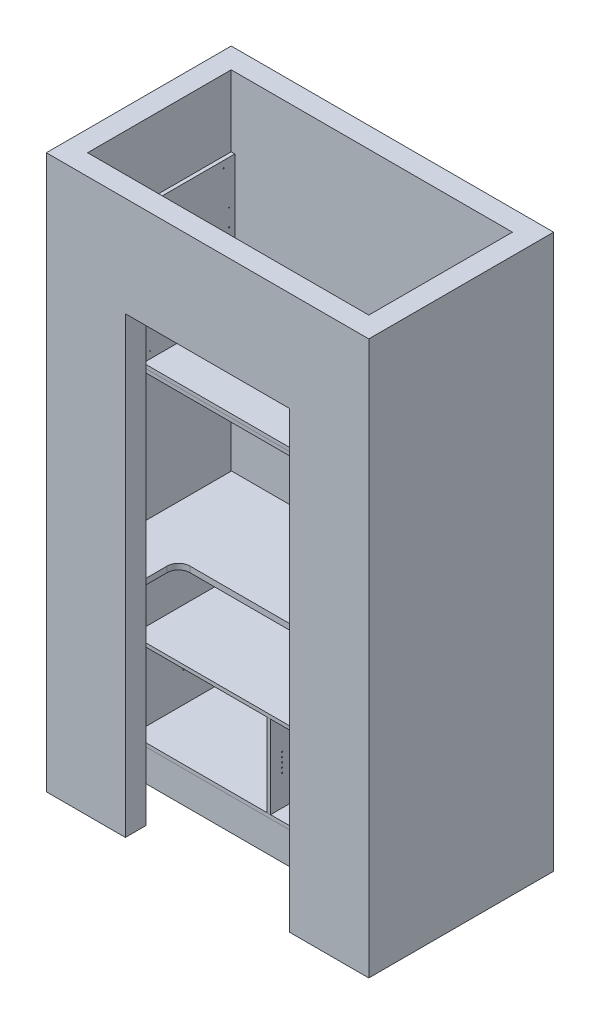
SolidWorks part; units mm, degrees
ref_plane "Front" through (0, 0, 0) normal (0, 0, 1) x (1, 0, 0)
ref_plane "Top" through (0, 0, 0) normal (0, 1, 0) x (1, 0, 0)
ref_plane "Right" through (0, 0, 0) normal (1, 0, 0) x (0, 0, -1)
sketch "Sketch1" plane through (0, 0, 0) normal (0, 1, 0) x (1, 0, 0)
  line L0 (-90, 90) -> (1317.5, 90)
  line L1 (0, 0) -> (1227.5, 0)
  line L2 (0, 0) -> (0, -627)
  line L3 (0, -627) -> (255, -627)
  line L4 (1227.5, 0) -> (1227.5, -627)
  line L5 (1317.5, 90) -> (1317.5, -717)
  line L6 (-90, -717) -> (255, -717)
  line L7 (-90, 90) -> (-90, -717)
  line L8 (255, -627) -> (255, -717)
  line L9 (972.5, -627) -> (972.5, -717)
  line L10 (972.5, -717) -> (1317.5, -717)
  line L11 (972.5, -627) -> (1227.5, -627)
  line L12 (-90, -717) -> (1317.5, -717) construction
  line L13 (255, -627) -> (972.5, -627)
  line L14 (0, -627) -> (1227.5, -627) construction
  line L15 (255, -717) -> (972.5, -717)
  dimension "D1" = 1227.5
  dimension "D2" = 627
  dimension "D4" = 255
  dimension "D5" = 255
  dimension "D3" = 90
extrude "Boss-Extrude1" add sketch "Sketch1" along normal blind 2416 contours L11 L9 L10 L5 L0 L7 L6 L8 L3 L2 L1 L4 | L8 L15 L9 L13 region at (613.75, 0, -73.7756) region at (613.75, 0, 672)
sketch "Sketch2" plane through (0, 0, 717) normal (0, 0, 1) x (1, 0, 0)
  line L0 (-90, 0) -> (1317.5, 0) construction
  line L1 (255, 0) -> (972.5, 0)
  line L2 (255, 0) -> (255, 1980)
  line L3 (255, 1980) -> (972.5, 1980)
  line L4 (972.5, 0) -> (972.5, 1980)
  line L5 (0, 2416) -> (0, 0) construction
  line L6 (1227.5, 2416) -> (1227.5, 0) construction
  dimension "D1" = 255
  dimension "D2" = 255
  dimension "D3" = 1980
  dimension "D4" = 717.5
extrude "Cut-Extrude1" cut sketch "Sketch2" against normal blind 100
sketch "Sketch4" plane through (0, 0, 0) normal (0, 0, 1) x (1, 0, 0)
  line L0 (1227.5, 2416) -> (1227.5, 0) construction
  line L5 (0, 120) -> (1227.5, 120)
  line L7 (16, 136) -> (1211.5, 136)
  line L9 (16, 513.5) -> (605.75, 513.5)
  line L11 (16, 497.5) -> (605.75, 497.5)
  line L13 (16, 875) -> (1211.5, 875)
  line L15 (16, 900) -> (1211.5, 900)
  line L21 (16, 1500) -> (1211.5, 1500)
  line L23 (16, 1516) -> (1211.5, 1516)
  line L25 (16, 1766) -> (1211.5, 1766)
  line L27 (16, 1782) -> (1211.5, 1782)
  line L37 (621.75, 513.5) -> (1211.5, 513.5)
  line L38 (621.75, 497.5) -> (1211.5, 497.5)
  line L39 (16, 1500) -> (0, 1500)
  line L40 (0, 120) -> (16, 120)
  line L41 (0, 120) -> (0, 2320)
  line L42 (598, 120) -> (613.75, 120)
  line L43 (605.75, 136) -> (605.75, 875)
  line L44 (605.75, 875) -> (614, 875)
  line L46 (614, 875) -> (621.75, 875)
  line L48 (613.75, 120) -> (630, 120)
  line L49 (621.75, 875) -> (621.75, 136)
  line L50 (0, 2320) -> (16, 2320)
  line L51 (16, 120) -> (16, 2320)
  line L52 (1211.5, 1500) -> (1227.5, 1500)
  line L54 (1227.5, 2320) -> (1227.5, 120)
  line L56 (1211.5, 2320) -> (1211.5, 120)
  line L57 (613.75, 136) -> (613.75, 171.2625) construction
  line L58 (1211.5, 2320) -> (1227.5, 2320)
  line L59 (-90, 0) -> (255, 0) construction
  line L60 (310.875, 513.5) -> (310.875, 875) construction
  line L61 (310.875, 497.5) -> (310.875, 136) construction
  dimension "D2" = 120
  dimension "D4" = 16
  dimension "D5" = 16
  dimension "D6" = 8
  dimension "D3" = 25
  dimension "D7" = 1500
  dimension "D8" = 250
  dimension "D9" = 16
  dimension "D10" = 2200
  dimension "D11" = 16
  dimension "D12" = 16
  dimension "D13" = 16
  dimension "D14" = 16
  dimension "D15" = 900
sketch "Sketch6" plane through (0, 0, 0) normal (0, 0, 1) x (1, 0, 0)
  line L0 (0, 120) -> (0, 2320) construction
  line L13 (16, 875) -> (0, 875)
  line L14 (16, 875) -> (16, 136)
  line L15 (16, 136) -> (0, 136)
  line L16 (0, 875) -> (0, 136)
  line L17 (16, 136) -> (1211.5, 136) construction
  line L18 (1227.5, 2320) -> (1227.5, 120) construction
  line L19 (1211.5, 875) -> (1227.5, 875)
  line L20 (1211.5, 875) -> (1211.5, 136)
  line L21 (1211.5, 136) -> (1227.5, 136)
  line L22 (1227.5, 875) -> (1227.5, 136)
  line L24 (605.75, 497.5) -> (621.75, 497.5)
  line L25 (605.75, 497.5) -> (605.75, 136)
  line L26 (605.75, 136) -> (621.75, 136)
  line L27 (621.75, 497.5) -> (621.75, 136)
extrude "Boss-Extrude2" add sketch "Sketch6" along normal blind 450 separate body
sketch "Sketch7" plane through (0, 0, 0) normal (0, 0, 1) x (1, 0, 0)
  line L0 (1227.5, 2320) -> (1227.5, 120) construction
  line L1 (0, 120) -> (1227.5, 120)
  line L2 (0, 120) -> (0, 136)
  line L3 (0, 136) -> (1227.5, 136)
  line L4 (1227.5, 120) -> (1227.5, 136)
  line L6 (16, 497.5) -> (16, 513.5)
  line L7 (16, 513.5) -> (1211.5, 513.5)
  line L9 (16, 497.5) -> (1211.5, 497.5)
  line L12 (1211.5, 497.5) -> (1211.5, 513.5)
  line L13 (0, 875) -> (1227.5, 875)
  line L14 (0, 875) -> (0, 900)
  line L15 (0, 900) -> (1227.5, 900)
  line L16 (1227.5, 875) -> (1227.5, 900)
  line L17 (16, 900) -> (1211.5, 900) construction
  line L19 (1211.5, 2320) -> (1211.5, 120) construction
  line L20 (16, 120) -> (16, 2320) construction
extrude "Boss-Extrude3" add sketch "Sketch7" along normal blind 450 separate body
sketch "Sketch8" plane through (0, 0, 0) normal (0, 0, 1) x (1, 0, 0)
  line L0 (0, 120) -> (0, 2320) construction
  line L1 (16, 1516) -> (0, 1516)
  line L2 (16, 1516) -> (16, 2106)
  line L3 (16, 2106) -> (0, 2106)
  line L4 (0, 1516) -> (0, 2106)
  line L5 (1227.5, 2320) -> (1227.5, 120) construction
  line L6 (1211.5, 1516) -> (1227.5, 1516)
  line L7 (1211.5, 1516) -> (1211.5, 2106)
  line L8 (1211.5, 2106) -> (1227.5, 2106)
  line L9 (1227.5, 1516) -> (1227.5, 2106)
  line L10 (16, 120) -> (16, 2320) construction
  dimension "D1" = 590
extrude "Boss-Extrude4" add sketch "Sketch8" along normal blind 400 separate body
sketch "Sketch9" plane through (0, 0, 0) normal (0, 0, 1) x (1, 0, 0)
  line L0 (1226.5, 1516) -> (1226.5, 1500)
  line L1 (16, 1782) -> (1211.5, 1782)
  line L2 (16, 1782) -> (16, 1766)
  line L3 (16, 1766) -> (1211.5, 1766)
  line L4 (1211.5, 1782) -> (1211.5, 1766)
  line L5 (1, 1516) -> (1226.5, 1516)
  line L6 (0, 1516) -> (0, 1500) construction
  line L7 (1, 1500) -> (1226.5, 1500)
  line L8 (1227.5, 1516) -> (1227.5, 1500) construction
  line L9 (1, 1516) -> (1, 1500)
  dimension "D1" = 1
  dimension "D2" = 1
extrude "Boss-Extrude5" add sketch "Sketch9" along normal blind 400 separate body
sketch "Sketch11" plane through (0, 900, 0) normal (0, 1, 0) x (1, 0, 0)
  line L0 (0, -450) -> (0, -627)
  line L1 (0, -627) -> (220, -627)
  line L2 (0, -627) -> (1227.5, -627) construction
  line L3 (220, -627) -> (220, -450)
  line L4 (1227.5, -450) -> (0, -450) construction
  line L5 (613.75, 90) -> (613.75, 254.9806) construction
  line L6 (-90, 90) -> (1317.5, 90) construction
  line L7 (0, -450) -> (220, -450)
  line L8 (1227.5, -450) -> (1007.5, -450)
  line L9 (1007.5, -627) -> (1007.5, -450)
  line L10 (1227.5, -627) -> (1007.5, -627)
  line L11 (1227.5, -450) -> (1227.5, -627)
  dimension "D1" = 220
extrude "Boss-Extrude6" add sketch "Sketch11" against normal up to surface (25 mm away) up to face at (613.75, 875, 225)
fillet "Fillet1" radius 50 2 edges at (220, 887.5, 450) (1007.5, 887.5, 450)
sketch "Sketch18" plane through (0, 120, 0) normal (0, -1, 0) x (1, 0, 0)
  line L0 (16, 0) -> (1211.5, 0) construction
  line L1 (0, 627) -> (1.25, 627)
  line L2 (0, 627) -> (0, 0)
  line L3 (0, 0) -> (1.25, 0)
  line L4 (1.25, 627) -> (1.25, 0)
  line L5 (1.25, 73.7952) -> (1226.25, 73.7952) construction
  line L6 (1227.5, 627) -> (1226.25, 627)
  line L7 (1227.5, 627) -> (1227.5, 0)
  line L8 (1227.5, 0) -> (1226.25, 0)
  line L9 (1226.25, 627) -> (1226.25, 0)
  line L10 (613.75, 73.7952) -> (613.75, -90) construction
  line L11 (-90, -90) -> (1317.5, -90) construction
  dimension "D1" = 1225
extrude "Cut-Extrude5" cut sketch "Sketch18" against normal through all
hole_wizard "Ø2.0 (2) Diameter Hole1" positions "Sketch20" profile "Sketch21" hole size "Ø2.0" standard "ISO"
sketch "Sketch20" plane through (0, 120, 0) normal (0, -1, 0) x (-1, 0, 0)
  line L1 (-645.75, -32) -> (-581.75, -32)
  line L2 (-645.75, -32) -> (-645.75, -96)
  line L3 (-645.75, -96) -> (-581.75, -96)
  line L4 (-581.75, -32) -> (-581.75, -96)
  line L7 (-613.75, -32) -> (-613.75, 0) construction
  line L8 (-1.25, 0) -> (-1226.25, 0) construction
  line L10 (0, 0) -> (-1227.5, 0) construction
  line L12 (-1176.25, -336.5) -> (-1112.25, -336.5)
  line L13 (-1176.25, -336.5) -> (-1176.25, -400.5)
  line L14 (-1176.25, -400.5) -> (-1112.25, -400.5)
  line L15 (-1112.25, -336.5) -> (-1112.25, -400.5)
  line L17 (-645.75, -336.5) -> (-581.75, -336.5)
  line L18 (-645.75, -336.5) -> (-645.75, -400.5)
  line L19 (-645.75, -400.5) -> (-581.75, -400.5)
  line L20 (-581.75, -336.5) -> (-581.75, -400.5)
  line L22 (-115.25, -336.5) -> (-51.25, -336.5)
  line L23 (-115.25, -336.5) -> (-115.25, -400.5)
  line L24 (-115.25, -400.5) -> (-51.25, -400.5)
  line L25 (-51.25, -336.5) -> (-51.25, -400.5)
  line L26 (-1226.25, -450) -> (-1226.25, 0) construction
  line L27 (-1.25, 0) -> (-1.25, -450) construction
  line L28 (-270, -450) -> (-957.5, -450) construction
  point P0 (-645.75, -32)
  point P2 (-581.75, -32)
  point P4 (-581.75, -96)
  point P6 (-645.75, -96)
  point P82 (-645.75, -400.5)
  point P84 (-645.75, -336.5)
  point P86 (-581.75, -336.5)
  point P88 (-581.75, -400.5)
  point P90 (-51.25, -400.5)
  point P92 (-51.25, -336.5)
  point P94 (-115.25, -336.5)
  point P96 (-115.25, -400.5)
  point P98 (-1176.25, -336.5)
  point P100 (-1112.25, -336.5)
  point P102 (-1112.25, -400.5)
  point P104 (-1176.25, -400.5)
  dimension "D1" = 50
  dimension "D2" = 64
  dimension "D3" = 50
  dimension "D4" = 49.5
  dimension "D5" = 64
  dimension "D6" = 32
sketch "Sketch21" plane through (645.75, 120, 32) normal (1, 0, 0) x (0, 0, -1)
  line L0 (0, 0) -> (0, 10.6009)
  line L1 (0, 10.6009) -> (1, 10)
  line L2 (1, 10) -> (1, 0)
  line L5 (1, 0) -> (0, 0)
  line L10 (0, 10.6009) -> (-1, 10) construction
  line L11 (0, -6.35) -> (0, 107.95) construction
  dimension "Hole Dia." = 2
  dimension "Hole Depth" = 10
  dimension "Drill Angle" = 118
hole_wizard "Ø2.0 (2) Diameter Hole2" positions "Sketch22" profile "Sketch23" hole size "Ø2.0" standard "ISO"
sketch "Sketch22" plane through (0, 120, 0) normal (0, -1, 0) x (-1, 0, 0)
  line L0 (-1219.5, -15) -> (-1219.5, -435) construction
  line L2 (-1227.5, 0) -> (-1227.5, -627) construction
  line L3 (0, 0) -> (0, -627) construction
  line L4 (-1.25, -450) -> (-1226.25, -450) construction
  line L5 (0, 0) -> (-1227.5, 0) construction
  line L6 (-613.75, -435) -> (-613.75, -450) construction
  line L7 (-270, -450) -> (-957.5, -450) construction
  point P0 (-1219.5, -435)
  point P2 (-1219.5, -225)
  point P4 (-1219.5, -15)
  point P6 (-613.75, -15)
  point P8 (-613.75, -225)
  point P10 (-613.75, -435)
  point P12 (-8, -15)
  point P14 (-8, -225)
  point P16 (-8, -435)
  dimension "D1" = 8
  dimension "D2" = 8
  dimension "D3" = 15
  dimension "D4" = 15
sketch "Sketch23" plane through (1219.5, 120, 435) normal (1, 0, 0) x (0, 0, -1)
  line L0 (0, 0) -> (0, 10.6009)
  line L1 (0, 10.6009) -> (1, 10)
  line L2 (1, 10) -> (1, 0)
  line L5 (1, 0) -> (0, 0)
  line L10 (0, 10.6009) -> (-1, 10) construction
  line L11 (0, -6.35) -> (0, 107.95) construction
  dimension "Hole Dia." = 2
  dimension "Hole Depth" = 10
  dimension "Drill Angle" = 118
sketch "Sketch24" plane through (0, 120, 0) normal (0, -1, 0) x (1, 0, 0)
  circle A0 centre (8, 435) radius 2.5
  circle A1 centre (8, 225) radius 2.5
  circle A2 centre (8, 15) radius 2.5
  circle A3 centre (613.75, 435) radius 2.5
  circle A4 centre (613.75, 225) radius 2.5
  circle A5 centre (613.75, 15) radius 2.5
  circle A6 centre (1219.5, 15) radius 2.5
  circle A7 centre (1219.5, 225) radius 2.5
  circle A8 centre (1219.5, 435) radius 2.5
  dimension "D1" = 5
extrude "Cut-Extrude6" cut sketch "Sketch24" against normal blind 1
sketch "Sketch25" plane through (16, 0, 0) normal (1, 0, 0) x (0, 0, -1)
  line L0 (-450, 497.5) -> (0, 497.5) construction
  line L1 (-450, 497.5) -> (0, 497.5) construction
  line L2 (-400, 497.5) -> (-50, 497.5) construction
  circle A0 centre (-400, 497.5) radius 2.5
  circle A1 centre (-50, 497.5) radius 2.5
  circle A2 centre (-225, 497.5) radius 2.5
  dimension "D1" = 5
  dimension "D2" = 350
extrude "Cut-Extrude7" cut sketch "Sketch25" against normal through all both and the other way through all
sketch "Sketch26" plane through (16, 0, 0) normal (1, 0, 0) x (0, 0, -1)
  line L0 (-400, 497.5) -> (-50, 497.5) construction
  circle A0 centre (-400, 308.75) radius 2.5
  circle A1 centre (-225, 308.75) radius 2.5
  circle A2 centre (-50, 308.75) radius 2.5
  circle A3 centre (-400, 497.5) radius 2.5 construction
  circle A4 centre (-400, 328.75) radius 2.5
  circle A5 centre (-225, 328.75) radius 2.5
  circle A6 centre (-50, 328.75) radius 2.5
  circle A7 centre (-400, 348.75) radius 2.5
  circle A8 centre (-225, 348.75) radius 2.5
  circle A9 centre (-50, 348.75) radius 2.5
  circle A10 centre (-400, 288.75) radius 2.5
  circle A11 centre (-225, 288.75) radius 2.5
  circle A12 centre (-50, 288.75) radius 2.5
  circle A13 centre (-400, 268.75) radius 2.5
  circle A14 centre (-225, 268.75) radius 2.5
  circle A15 centre (-50, 268.75) radius 2.5
  dimension "D1" = 188.75
  dimension "D2" = 3
  dimension "D3" = 3
extrude "Cut-Extrude8" cut sketch "Sketch26" against normal through all both and the other way through all
sketch "Sketch34" plane through (0, 497.5, 0) normal (0, -1, 0) x (1, 0, 0)
  line L0 (16, 450) -> (16, 0) construction
  line L1 (16, 403) -> (39.6625, 403)
  line L2 (16, 403) -> (16, 397)
  line L3 (16, 397) -> (39.6625, 397)
  line L4 (41.25, 401.4125) -> (41.25, 398.5875)
  line L15 (16, 400) -> (41.25, 400) construction
  line L16 (1.25, 0) -> (1.25, 450) construction
  line L17 (0, 400) -> (16, 400) construction
  line L18 (16, 228) -> (39.6625, 228)
  line L19 (16, 228) -> (16, 222)
  line L20 (16, 222) -> (39.6625, 222)
  line L21 (41.25, 226.4125) -> (41.25, 223.5875)
  line L22 (16, 225) -> (41.25, 225) construction
  line L23 (16, 53) -> (39.6625, 53)
  line L24 (16, 53) -> (16, 47)
  line L25 (16, 47) -> (39.6625, 47)
  line L26 (41.25, 51.4125) -> (41.25, 48.5875)
  line L27 (16, 50) -> (41.25, 50) construction
  line L28 (613.75, 435) -> (613.75, 225) construction
  line L29 (1211.5, 50) -> (1186.25, 50) construction
  line L30 (1211.5, 225) -> (1186.25, 225) construction
  line L31 (1211.5, 400) -> (1186.25, 400) construction
  line L32 (1186.25, 51.4125) -> (1186.25, 48.5875)
  line L33 (1211.5, 47) -> (1187.8375, 47)
  line L34 (1211.5, 53) -> (1211.5, 47)
  line L35 (1211.5, 53) -> (1187.8375, 53)
  line L36 (1186.25, 226.4125) -> (1186.25, 223.5875)
  line L37 (1211.5, 222) -> (1187.8375, 222)
  line L38 (1211.5, 228) -> (1211.5, 222)
  line L39 (1211.5, 228) -> (1187.8375, 228)
  line L40 (1186.25, 401.4125) -> (1186.25, 398.5875)
  line L41 (1211.5, 397) -> (1187.8375, 397)
  line L42 (1211.5, 403) -> (1211.5, 397)
  line L43 (1211.5, 403) -> (1187.8375, 403)
  arc A0 (39.6625, 397) -> (41.25, 398.5875) centre (39.6625, 398.5875) ccw
  arc A1 (39.6625, 403) -> (41.25, 401.4125) centre (39.6625, 401.4125) cw
  arc A2 (39.6625, 222) -> (41.25, 223.5875) centre (39.6625, 223.5875) ccw
  arc A3 (39.6625, 228) -> (41.25, 226.4125) centre (39.6625, 226.4125) cw
  arc A4 (39.6625, 47) -> (41.25, 48.5875) centre (39.6625, 48.5875) ccw
  arc A5 (39.6625, 53) -> (41.25, 51.4125) centre (39.6625, 51.4125) cw
  arc A6 (1187.8375, 53) -> (1186.25, 51.4125) centre (1187.8375, 51.4125) ccw
  arc A7 (1187.8375, 47) -> (1186.25, 48.5875) centre (1187.8375, 48.5875) cw
  arc A8 (1187.8375, 228) -> (1186.25, 226.4125) centre (1187.8375, 226.4125) ccw
  arc A9 (1187.8375, 222) -> (1186.25, 223.5875) centre (1187.8375, 223.5875) cw
  arc A10 (1187.8375, 403) -> (1186.25, 401.4125) centre (1187.8375, 401.4125) ccw
  arc A11 (1187.8375, 397) -> (1186.25, 398.5875) centre (1187.8375, 398.5875) cw
  point P26 (41.25, 397)
  point P29 (41.25, 403)
  point P73 (1186.25, 403)
  point P74 (1186.25, 397)
  dimension "D3" = 1.5875
  dimension "D1" = 40
  dimension "D2" = 6
  dimension "D4" = 3
extrude "Cut-Extrude9" cut sketch "Sketch34" against normal blind 3
hole_wizard "Ø2.0 (2) Diameter Hole3" positions "Sketch35" profile "Sketch36" hole size "Ø2.0" standard "ISO"
sketch "Sketch35" plane through (621.75, 0, 0) normal (1, 0, 0) x (0, 0, -1)
  line L0 (-450, 136) -> (-450, 497.5) construction
  line L1 (-450, 497.5) -> (0, 497.5) construction
  line L2 (0, 875) -> (0, 136) construction
  point P0 (-400, 481.5)
  point P7 (-100, 481.5)
  dimension "D1" = 50
  dimension "D2" = 16
  dimension "D3" = 100
sketch "Sketch36" plane through (621.75, 481.5, 400) normal (0, 1, 0) x (0, 0, -1)
  line L0 (0, 0) -> (0, 18.6009)
  line L1 (0, 18.6009) -> (1, 18)
  line L2 (1, 18) -> (1, 0)
  line L5 (1, 0) -> (0, 0)
  line L10 (0, 18.6009) -> (-1, 18) construction
  line L11 (0, -6.35) -> (0, 107.95) construction
  dimension "Hole Dia." = 2
  dimension "Hole Depth" = 18
  dimension "Drill Angle" = 118
hole_wizard "Ø2.0 (2) Diameter Hole4" positions "Sketch37" profile "Sketch38" hole size "Ø2.0" standard "ISO" end condition through all
sketch "Sketch37" plane through (1317.5, 0, 0) normal (1, 0, 0) x (0, 0, -1)
  line L0 (-450, 136) -> (-450, 875) construction
  line L1 (0, 120) -> (0, 2320) construction
  line L2 (-450, 875) -> (0, 875) construction
  line L3 (-450, 136) -> (0, 136) construction
  point P0 (-425, 171)
  point P2 (-425, 471)
  point P4 (-425, 825)
  point P6 (-50, 825)
  point P10 (-50, 171)
  dimension "D1" = 25
  dimension "D2" = 50
  dimension "D3" = 50
  dimension "D4" = 35
  dimension "D5" = 300
sketch "Sketch38" plane through (1317.5, 171, 425) normal (0, 1, 0) x (0, 0, -1)
  line L0 (0, 0) -> (0, 1407.5)
  line L1 (0, 1407.5) -> (1, 1407.5)
  line L2 (1, 1407.5) -> (1, 0)
  line L5 (1, 0) -> (0, 0)
  line L11 (0, -6.35) -> (0, 107.95) construction
  dimension "Thru Hole Dia." = 2
  dimension "Thru Hole Depth" = 1407.5
sketch "Sketch39" plane through (16, 0, 0) normal (1, 0, 0) x (0, 0, -1)
  circle A0 centre (-425, 171) radius 2.5
  circle A1 centre (-50, 171) radius 2.5
  circle A2 centre (-425, 471) radius 2.5
  circle A3 centre (-425, 825) radius 2.5
  circle A4 centre (-50, 825) radius 2.5
  dimension "D1" = 5
extrude "Cut-Extrude10" cut sketch "Sketch39" against normal blind 1
sketch "Sketch40" plane through (1211.5, 0, 0) normal (-1, 0, 0) x (0, 0, 1)
  circle A1 centre (50, 825) radius 2.5
  circle A2 centre (50, 825) radius 2.5
  circle A3 centre (425, 825) radius 2.5
  circle A4 centre (425, 825) radius 2.5
  circle A5 centre (425, 471) radius 2.5
  circle A6 centre (425, 471) radius 2.5
  circle A7 centre (50, 171) radius 2.5
  circle A8 centre (50, 171) radius 2.5
  circle A9 centre (425, 171) radius 2.5
  circle A10 centre (425, 171) radius 2.5
  dimension "D1" = 0
  dimension "D2" = 0
  dimension "D3" = 0
  dimension "D4" = 0
  dimension "D5" = 0
extrude "Cut-Extrude11" cut sketch "Sketch40" against normal blind 1
sketch "Sketch41" plane through (0, 1782, 0) normal (0, 1, 0) x (1, 0, 0)
  line L0 (1211.5, -400) -> (16, -400) construction
  line L1 (16, 0) -> (17, 0)
  line L2 (16, 0) -> (16, -400)
  line L3 (16, -400) -> (17, -400)
  line L4 (17, 0) -> (17, -400)
  line L6 (1211.5, 0) -> (1210.5, 0)
  line L7 (1211.5, 0) -> (1211.5, -400)
  line L8 (1211.5, -400) -> (1210.5, -400)
  line L9 (1210.5, 0) -> (1210.5, -400)
  dimension "D1" = 1
  dimension "D2" = 1
extrude "Cut-Extrude12" cut sketch "Sketch41" against normal up to next (16 mm away)
hole_wizard "Ø2.0 (2) Diameter Hole5" positions "Sketch42" profile "Sketch43" hole size "Ø2.0" standard "ISO" end condition through all
sketch "Sketch42" plane through (0, 1500, 0) normal (0, -1, 0) x (-1, 0, 0)
  line L0 (-1227.5, -400) -> (-1227.5, 0) construction
  line L1 (0, -400) -> (0, 0) construction
  line L2 (-1, -400) -> (-1226.5, -400) construction
  line L3 (0, 0) -> (-16, 0) construction
  point P0 (-1219.5, -380)
  point P2 (-1219.5, -200)
  point P4 (-1219.5, -20)
  point P6 (-8, -380)
  point P8 (-8, -200)
  point P10 (-8, -20)
  dimension "D1" = 8
  dimension "D2" = 8
  dimension "D3" = 20
  dimension "D4" = 20
  dimension "D5" = 180
sketch "Sketch43" plane through (1219.5, 1500, 380) normal (1, 0, 0) x (0, 0, -1)
  line L0 (0, 0) -> (0, 916)
  line L1 (0, 916) -> (1, 916)
  line L2 (1, 916) -> (1, 0)
  line L5 (1, 0) -> (0, 0)
  line L11 (0, -6.35) -> (0, 107.95) construction
  dimension "Thru Hole Dia." = 2
  dimension "Thru Hole Depth" = 916
sketch "Sketch44" plane through (0, 1500, 0) normal (0, -1, 0) x (1, 0, 0)
  circle A0 centre (8, 380) radius 2.5
  circle A1 centre (8, 200) radius 2.5
  circle A2 centre (8, 20) radius 2.5
  circle A3 centre (1219.5, 20) radius 2.5
  circle A4 centre (1219.5, 200) radius 2.5
  circle A5 centre (1219.5, 380) radius 2.5
  dimension "D1" = 5
extrude "Cut-Extrude13" cut sketch "Sketch44" against normal blind 1
hole_wizard "Ø5.0 (5) Diameter Hole1" positions "Sketch45" profile "Sketch46" hole size "Ø5.0" standard "ISO" end condition through all
sketch "Sketch45" plane through (1227.5, 0, 0) normal (1, 0, 0) x (0, 0, -1)
  line L0 (-400, 1766) -> (0, 1766) construction
  line L1 (-400, 1516) -> (-400, 2106) construction
  line L2 (0, 120) -> (0, 2320) construction
  point P0 (-375, 1766)
  point P4 (-200, 1766)
  point P6 (-25, 1766)
  point P8 (-375, 1841)
  point P10 (-200, 1841)
  point P12 (-25, 1841)
  point P14 (-375, 1916)
  point P16 (-200, 1916)
  point P18 (-25, 1916)
  dimension "D1" = 25
  dimension "D2" = 25
  dimension "D3" = 75
  dimension "D4" = 75
sketch "Sketch46" plane through (1227.5, 1766, 375) normal (0, 1, 0) x (0, 0, -1)
  line L0 (0, 0) -> (0, 1317.5)
  line L1 (0, 1317.5) -> (2.5, 1317.5)
  line L2 (2.5, 1317.5) -> (2.5, 0)
  line L5 (2.5, 0) -> (0, 0)
  line L11 (0, -6.35) -> (0, 107.95) construction
  dimension "Thru Hole Dia." = 5
  dimension "Thru Hole Depth" = 1317.5
hole_wizard "Ø2.0 (2) Diameter Hole6" positions "Sketch48" profile "Sketch49" hole size "Ø2.0" standard "ISO" end condition through all
sketch "Sketch48" plane through (1227.5, 0, 0) normal (1, 0, 0) x (0, 0, -1)
  line L0 (-400, 1516) -> (0, 1516) construction
  line L1 (-400, 1516) -> (-400, 2106) construction
  line L2 (0, 120) -> (0, 2320) construction
  line L3 (-400, 2106) -> (0, 2106) construction
  circle A0 centre (-375, 1766) radius 2.5 construction
  point P0 (-370, 1546)
  point P2 (-370, 2076)
  point P4 (-370, 1801)
  point P6 (-50, 1546)
  point P8 (-50, 1801)
  point P10 (-50, 2076)
  dimension "D1" = 30
  dimension "D2" = 30
  dimension "D3" = 50
  dimension "D4" = 35
  dimension "D5" = 30
sketch "Sketch49" plane through (1227.5, 1546, 370) normal (0, 1, 0) x (0, 0, -1)
  line L0 (0, 0) -> (0, 1317.5)
  line L1 (0, 1317.5) -> (1, 1317.5)
  line L2 (1, 1317.5) -> (1, 0)
  line L5 (1, 0) -> (0, 0)
  line L11 (0, -6.35) -> (0, 107.95) construction
  dimension "Thru Hole Dia." = 2
  dimension "Thru Hole Depth" = 1317.5
sketch "Sketch50" plane through (16, 0, 0) normal (1, 0, 0) x (0, 0, -1)
  circle A0 centre (-370, 2076) radius 2.5
  circle A1 centre (-50, 2076) radius 2.5
  circle A2 centre (-50, 1801) radius 2.5
  circle A3 centre (-370, 1801) radius 2.5
  circle A4 centre (-370, 1546) radius 2.5
  circle A5 centre (-50, 1546) radius 2.5
  dimension "D1" = 5
extrude "Cut-Extrude14" cut sketch "Sketch50" against normal blind 1
sketch "Sketch51" plane through (1211.5, 0, 0) normal (-1, 0, 0) x (0, 0, 1)
  circle A1 centre (370, 1546) radius 2.5
  circle A2 centre (370, 1546) radius 2.5
  circle A3 centre (370, 1801) radius 2.5
  circle A4 centre (370, 1801) radius 2.5
  circle A5 centre (50, 1801) radius 2.5
  circle A6 centre (50, 1801) radius 2.5
  circle A7 centre (50, 2076) radius 2.5
  circle A8 centre (50, 2076) radius 2.5
  circle A9 centre (370, 2076) radius 2.5
  circle A10 centre (370, 2076) radius 2.5
  circle A11 centre (50, 1546) radius 2.5
  circle A12 centre (50, 1546) radius 2.5
  dimension "D1" = 0
  dimension "D2" = 0
  dimension "D3" = 0
  dimension "D4" = 0
  dimension "D5" = 0
  dimension "D6" = 0
extrude "Cut-Extrude15" cut sketch "Sketch51" against normal blind 1
sketch "Sketch52" plane through (0, 1766, 0) normal (0, -1, 0) x (1, 0, 0)
  line L0 (17, 0) -> (17, 400) construction
  line L1 (17, 378) -> (38.4125, 378)
  line L2 (17, 378) -> (17, 372)
  line L3 (17, 372) -> (38.4125, 372)
  line L4 (40, 376.4125) -> (40, 373.5875)
  line L5 (17, 375) -> (40, 375) construction
  line L6 (0, 400) -> (0, 0) construction
  line L7 (17, 400) -> (1210.5, 400) construction
  line L9 (613.75, 435) -> (613.75, -96.6075) construction
  line L13 (17, 203) -> (38.4125, 203)
  line L18 (17, 203) -> (17, 197)
  line L19 (17, 197) -> (38.4125, 197)
  line L20 (40, 201.4125) -> (40, 198.5875)
  line L21 (17, 200) -> (40, 200) construction
  line L22 (17, 28) -> (38.4125, 28)
  line L23 (17, 28) -> (17, 22)
  line L24 (17, 22) -> (38.4125, 22)
  line L25 (40, 26.4125) -> (40, 23.5875)
  line L26 (17, 25) -> (40, 25) construction
  line L27 (1210.5, 25) -> (1187.5, 25) construction
  line L28 (1210.5, 200) -> (1187.5, 200) construction
  line L29 (1210.5, 375) -> (1187.5, 375) construction
  line L30 (1187.5, 26.4125) -> (1187.5, 23.5875)
  line L31 (1210.5, 22) -> (1189.0875, 22)
  line L32 (1210.5, 28) -> (1210.5, 22)
  line L33 (1210.5, 28) -> (1189.0875, 28)
  line L34 (1187.5, 201.4125) -> (1187.5, 198.5875)
  line L35 (1210.5, 197) -> (1189.0875, 197)
  line L36 (1210.5, 203) -> (1210.5, 197)
  line L37 (1210.5, 203) -> (1189.0875, 203)
  line L38 (1187.5, 376.4125) -> (1187.5, 373.5875)
  line L39 (1210.5, 372) -> (1189.0875, 372)
  line L40 (1210.5, 378) -> (1210.5, 372)
  line L41 (1210.5, 378) -> (1189.0875, 378)
  arc A0 (38.4125, 372) -> (40, 373.5875) centre (38.4125, 373.5875) ccw
  arc A1 (38.4125, 378) -> (40, 376.4125) centre (38.4125, 376.4125) cw
  arc A6 (38.4125, 197) -> (40, 198.5875) centre (38.4125, 198.5875) ccw
  arc A7 (38.4125, 203) -> (40, 201.4125) centre (38.4125, 201.4125) cw
  arc A8 (38.4125, 22) -> (40, 23.5875) centre (38.4125, 23.5875) ccw
  arc A9 (38.4125, 28) -> (40, 26.4125) centre (38.4125, 26.4125) cw
  arc A10 (1189.0875, 28) -> (1187.5, 26.4125) centre (1189.0875, 26.4125) ccw
  arc A11 (1189.0875, 22) -> (1187.5, 23.5875) centre (1189.0875, 23.5875) cw
  arc A12 (1189.0875, 203) -> (1187.5, 201.4125) centre (1189.0875, 201.4125) ccw
  arc A13 (1189.0875, 197) -> (1187.5, 198.5875) centre (1189.0875, 198.5875) cw
  arc A14 (1189.0875, 378) -> (1187.5, 376.4125) centre (1189.0875, 376.4125) ccw
  arc A15 (1189.0875, 372) -> (1187.5, 373.5875) centre (1189.0875, 373.5875) cw
  dimension "D1" = 1.5875
  dimension "D2" = 6
  dimension "D3" = 40
  dimension "D4" = 25
  dimension "D5" = 3
extrude "Cut-Extrude16" cut sketch "Sketch52" against normal blind 3
sketch "Sketch54" plane through (0, 0, 450) normal (0, 0, 1) x (1, 0, 0)
  line L0 (1226.25, 120) -> (1226.25, 136) construction
  line L1 (1.25, 120) -> (1226.25, 120)
  line L2 (1.25, 120) -> (1.25, -19)
  line L3 (1.25, -19) -> (1226.25, -19)
  line L4 (1226.25, 120) -> (1226.25, -19)
  dimension "D1" = 139
extrude "Boss-Extrude7" add sketch "Sketch54" against normal blind 16 separate body
sketch "Sketch55" plane through (0, 0, 434) normal (0, 0, -1) x (-1, 0, 0)
  line L0 (-1226.25, 120) -> (-1.25, 120) construction
  line L1 (-1169.25, 80) -> (-1119.25, 80)
  line L3 (-1169.25, 77) -> (-1119.25, 77)
  line L5 (-108.25, 80) -> (-58.25, 80)
  line L7 (-108.25, 77) -> (-58.25, 77)
  line L8 (-1144.25, 80) -> (-1144.25, -56.6281) construction
  line L9 (-1226.25, -19) -> (-1226.25, 120) construction
  line L10 (-83.25, 80) -> (-83.25, 123.5184) construction
  line L11 (-1.25, 120) -> (-1.25, -19) construction
  arc A0 (-1169.25, 80) -> (-1169.25, 77) centre (-1169.25, 78.5) ccw
  arc A1 (-1119.25, 77) -> (-1119.25, 80) centre (-1119.25, 78.5) ccw
  arc A2 (-108.25, 80) -> (-108.25, 77) centre (-108.25, 78.5) ccw
  arc A3 (-58.25, 77) -> (-58.25, 80) centre (-58.25, 78.5) ccw
  dimension "D1" = 3
  dimension "D2" = 50
  dimension "D3" = 40
  dimension "D4" = 3
  dimension "D5" = 82
  dimension "D6" = 82
extrude "Cut-Extrude17" cut sketch "Sketch55" against normal blind 8
sketch "Sketch56" plane through (0, 0, 400) normal (0, 0, 1) x (1, 0, 0)
  line L0 (1, 1516) -> (1, 1500) construction
  line L1 (1226.5, 1500) -> (1, 1500)
  line L2 (1226.5, 1500) -> (1226.5, 1484)
  line L3 (1226.5, 1484) -> (1, 1484)
  line L4 (1, 1500) -> (1, 1484)
  dimension "D1" = 16
extrude "Boss-Extrude8" add sketch "Sketch56" against normal blind 100 separate body
delete or keep bodies "Body-Delete/Keep 1" [suppressed] type delete bodies bodies 102
delete or keep bodies "Body-Delete/Keep 2" [suppressed] type keep bodies bodies 124
delete or keep bodies "Body-Delete/Keep 3" [suppressed] type keep bodies bodies 127
delete or keep bodies "Body-Delete/Keep 4" [suppressed] type keep bodies bodies 147
delete or keep bodies "Body-Delete/Keep 5" [suppressed] type keep bodies bodies 148
delete or keep bodies "Body-Delete/Keep 6" [suppressed] type keep bodies bodies 151
delete or keep bodies "Body-Delete/Keep 7" [suppressed] type keep bodies bodies 152
delete or keep bodies "Body-Delete/Keep 8" [suppressed] type keep bodies bodies 157
delete or keep bodies "Body-Delete/Keep 9" [suppressed] type keep bodies bodies 163
delete or keep bodies "Body-Delete/Keep 10" [suppressed] type keep bodies bodies 164
delete or keep bodies "Body-Delete/Keep 11" [suppressed] type keep bodies bodies 165
delete or keep bodies "Body-Delete/Keep 12" [suppressed] type keep bodies bodies 167
